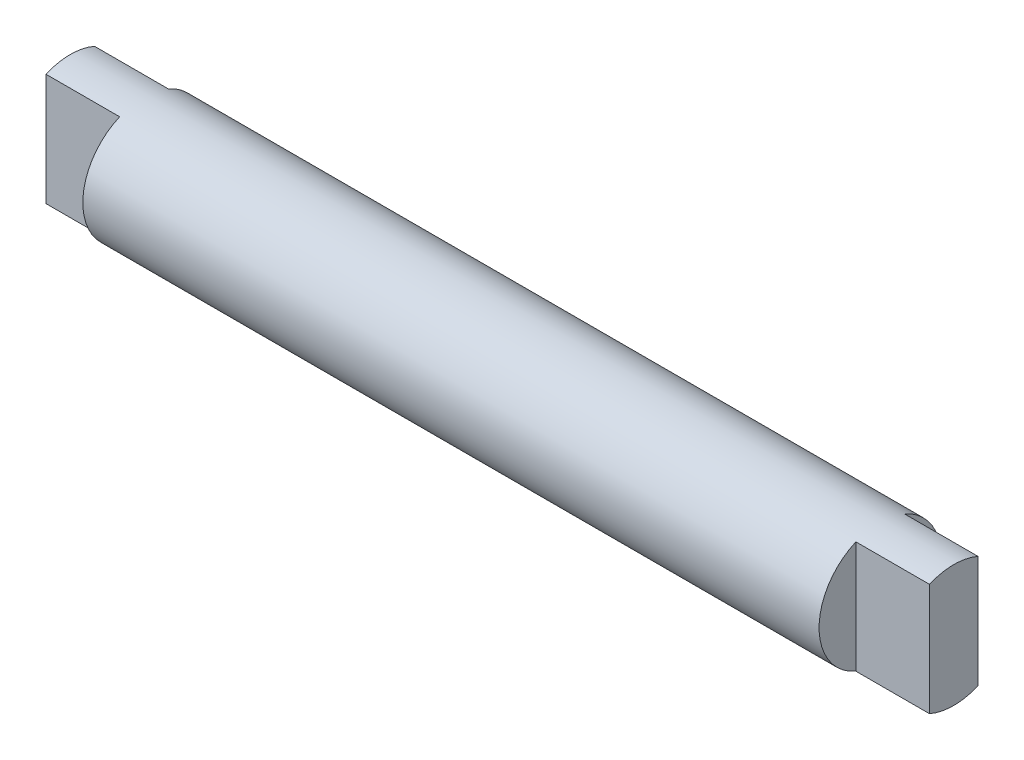
SolidWorks part; units mm, degrees
ref_plane "Front Plane" through (0, 0, 0) normal (0, 0, 1) x (1, 0, 0)
ref_plane "Top Plane" through (0, 0, 0) normal (0, 1, 0) x (1, 0, 0)
ref_plane "Right Plane" through (0, 0, 0) normal (1, 0, 0) x (0, 0, -1)
sketch "Sketch4" plane through (0, 0, 0) normal (1, 0, 0) x (0, 0, -1)
  circle A0 centre (0, 0) radius 21.064
extrude "Boss-Extrude2" add sketch "Sketch4" along normal blind 292.1 and the other way blind 12.7
sketch "Sketch5" plane through (0, 0, 0) normal (0, 1, 0) x (1, 0, 0)
  line L1 (-12.7, -21.064) -> (12.7, -21.064)
  line L2 (-12.7, -21.064) -> (-12.7, -8.364)
  line L3 (-12.7, -8.364) -> (12.7, -8.364)
  line L4 (12.7, -21.064) -> (12.7, -8.364)
  line L5 (-12.7, 21.064) -> (12.7, 21.064)
  line L6 (-12.7, 21.064) -> (-12.7, 8.364)
  line L7 (-12.7, 8.364) -> (12.7, 8.364)
  line L8 (12.7, 21.064) -> (12.7, 8.364)
  line L9 (292.1, 21.064) -> (266.7, 21.064)
  line L10 (292.1, 21.064) -> (292.1, 8.364)
  line L11 (292.1, 8.364) -> (266.7, 8.364)
  line L12 (266.7, 21.064) -> (266.7, 8.364)
  line L13 (292.1, -21.064) -> (266.7, -21.064)
  line L14 (292.1, -21.064) -> (292.1, -8.364)
  line L15 (292.1, -8.364) -> (266.7, -8.364)
  line L16 (266.7, -21.064) -> (266.7, -8.364)
  dimension "D1" = 25.4
  dimension "D2" = 12.7
extrude "Cut-Extrude2" cut sketch "Sketch5" against normal through all both and the other way through all
